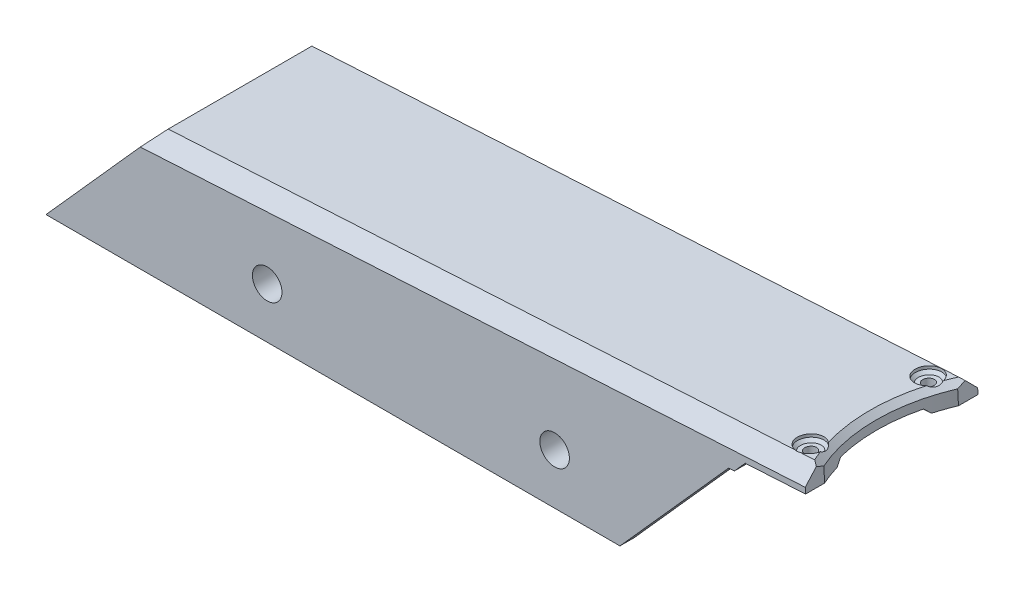
SolidWorks part; units mm, degrees
ref_plane "Plan de face" through (0, 0, 0) normal (0, 0, 1) x (1, 0, 0)
ref_plane "Plan de dessus" through (0, 0, 0) normal (0, 1, 0) x (1, 0, 0)
ref_plane "Plan de droite" through (0, 0, 0) normal (1, 0, 0) x (0, 0, -1)
sketch "Esquisse1" plane through (0, 0, 0) normal (0, 0, 1) x (1, 0, 0)
  line L0 (-49.925, 0) -> (49.925, 0)
  line L1 (-49.925, 0) -> (-36.817, 14.6872)
  line L2 (49.925, 0) -> (68.3667, 20.6636)
  line L3 (68.3667, 20.6636) -> (-36.817, 14.6872)
  point P4 (0, 0)
  dimension "D1" = 99.85
  dimension "D2" = 131.748
  dimension "D3" = 45
  dimension "D4" = 48.252
  dimension "D5" = 19.6859
extrude "Boss.-Extru.1" add sketch "Esquisse1" against normal blind 5
sketch "Esquisse2" plane through (0, 0, 0) normal (0, 0, 1) x (1, 0, 0)
  line L0 (-36.817, 14.6872) -> (68.3667, 20.6636)
  line L1 (68.3667, 20.6636) -> (-36.817, 14.6872) construction
  line L2 (68.3667, 20.6636) -> (74.0167, 26.9943)
  line L3 (74.0167, 26.9943) -> (-31.1671, 21.0179)
  line L4 (-31.1671, 21.0179) -> (-36.817, 14.6872)
  line L5 (-36.817, 14.6872) -> (-49.925, 0) construction
  line L6 (49.925, 0) -> (68.3667, 20.6636) construction
  line L11 (74.0167, 26.9943) -> (82.0167, 27.4488)
  line L12 (82.0167, 27.4488) -> (82.1585, 24.9528)
  line L13 (82.1585, 24.9528) -> (71.6625, 24.3565)
  line L22 (71.6625, 24.3565) -> (74.0167, 26.9943)
  dimension "D1" = 2.5
  dimension "D2" = 6
  dimension "D4" = 45
  dimension "D5" = 8
extrude "Boss.-Extru.2" add sketch "Esquisse2" against normal blind 5 contours L3 L4 L0 L2 | L13 L12 L11 L2 region at (18.5998, 20.8408, 0) region at (77.4387, 25.8804, 0)
sketch "Esquisse3" plane through (0, 0, -5) normal (0, 0, -1) x (-1, 0, 0)
  line L0 (-82.0167, 27.4488) -> (31.1671, 21.0179)
  line L1 (-82.0167, 27.4488) -> (31.1671, 21.0179) construction
  line L2 (-82.0167, 27.4488) -> (-82.1585, 24.9528)
  line L3 (-82.1585, 24.9528) -> (33.5212, 18.3801)
  line L4 (33.5212, 18.3801) -> (31.1671, 21.0179)
  line L5 (-82.0167, 27.4488) -> (-82.1585, 24.9528) construction
  line L9 (31.1671, 21.0179) -> (49.925, 0) construction
extrude "Boss.-Extru.3" add sketch "Esquisse3" along normal blind 25
sketch "Esquisse4" plane through (-1.1488, 20.2195, 0) normal (0.0567, -0.9984, 0) x (0.9984, 0.0567, 0)
  line L0 (83.4417, 0) -> (72.9288, 0)
  line L1 (72.9288, 0) -> (72.9288, -7.8)
  line L2 (72.9288, -7.8) -> (83.4417, -7.8)
  line L3 (83.4417, -7.8) -> (83.4417, 0)
  line L4 (83.4417, -30) -> (83.4417, 0) construction
  line L5 (83.4417, 0) -> (72.9288, 0) construction
  line L6 (72.9288, -5) -> (72.9288, 0) construction
  line L7 (72.9288, -22.2) -> (83.4417, -22.2)
  line L12 (100.4529, -15) -> (66.4305, -15) construction
  line L13 (72.9288, -30) -> (72.9288, -22.2)
  line L14 (83.4417, -30) -> (72.9288, -30)
  line L15 (83.4417, -22.2) -> (83.4417, -30)
  point P20 (83.4417, -15)
  dimension "D1" = 7.8
extrude "Boss.-Extru.4" add sketch "Esquisse4" along normal blind 1
sketch "Esquisse5" plane through (-1.1488, 20.2195, 0) normal (0.0567, -0.9984, 0) x (0.9984, 0.0567, 0)
  circle A0 centre (79.7412, -25.2117) radius 1
  circle A1 centre (79.7412, -4.7117) radius 1
  dimension "D1" = 2
extrude "Enlèv. mat.-Extru.1" cut sketch "Esquisse5" against normal through all both and the other way through all contours A1 | A0
sketch "Esquisse9" plane through (-1.2907, 22.7155, 0) normal (-0.0567, 0.9984, 0) x (0.9984, 0.0567, 0)
  circle A0 centre (79.7412, 25.2117) radius 2.25
  circle A1 centre (79.7412, 4.7117) radius 2.25
  dimension "D1" = 4.5
extrude "Enlèv. mat.-Extru.2" cut sketch "Esquisse9" against normal blind 1
sketch "Esquisse6" plane through (-1.1488, 20.2195, 0) normal (0.0567, -0.9984, 0) x (0.9984, 0.0567, 0)
  line L0 (83.4417, -3.3188) -> (83.4417, -26.6046)
  line L4 (83.4417, -30) -> (83.4417, 0) construction
  arc A0 (83.4417, -26.6046) -> (83.4417, -3.3188) centre (108.7412, -14.9617) cw
  point P11 (83.4417, -14.9617)
  dimension "D1" = 27.85
extrude "Enlèv. mat.-Extru.3" cut sketch "Esquisse6" against normal through all and the other way through all
sketch "Esquisse13" plane through (0, 0, 0) normal (0, 0, 1) x (1, 0, 0)
  circle A0 centre (38.5577, 8.8036) radius 2.575
  circle A1 centre (-11.4423, 8.8036) radius 2.575
  dimension "D1" = 5.15
extrude "Enlèv. mat.-Extru.4" cut sketch "Esquisse13" against normal through all both and the other way through all
sketch "Esquisse7" plane through (-1.1488, 20.2195, 0) normal (0.0567, -0.9984, 0) x (0.9984, 0.0567, 0)
  line L0 (72.9288, 0) -> (72.9288, -30)
  line L1 (72.9288, -30) -> (-32.4246, -30)
  line L2 (-32.4246, -30) -> (-32.4246, 0)
  line L3 (-32.4246, 0) -> (72.9288, 0)
  line L4 (-32.4246, -30) -> (72.9288, -30) construction
  line L6 (83.4417, 0) -> (-29.9246, 0) construction
  line L7 (-32.4246, -30) -> (-32.4246, -5) construction
  line L8 (72.9288, 0) -> (72.9288, -7.8) construction
extrude "Boss.-Extru.5" add sketch "Esquisse7" along normal blind 3
chamfer "Chanfrein1" distance 2.5 angle 45 1 edges at (-41.7231, 9.1901, -5)
chamfer "Chanfrein2" distance 2.5 angle 45 1 edges at (59.3813, 10.5956, -5)
chamfer "Chanfrein3" distance 2.7 angle 60 1 edges at (16.2457, 18.203, -5) first distance on face at (35.9827, 8.8036, -5)
chamfer "Chanfrein4" distance 2.5 angle 45 1 edges at (25.4248, 24.2334, 0)
chamfer "Chanfrein5" distance 2.5 angle 45 1 edges at (25.4248, 24.2334, -30)
chamfer "Chanfrein6" distance 0.5 angle 45 2 edges at (76.1325, 26.1129, -4.7117) (76.1325, 26.1129, -25.2117)
chamfer "Chanfrein7" distance 1 angle 45 1 edges at (79.4703, 27.3041, -14.9617)
chamfer "Chanfrein8" distance 2 angle 45 2 edges at (71.8327, 21.3613, -15) (19.2408, 18.3731, -30)
chamfer "Chanfrein9" distance 1 angle 45 1 edges at (76.1616, 23.6105, -7.8)
chamfer "Chanfrein10" distance 1 angle 45 1 edges at (76.1718, 23.6111, -22.2)
equation "\"3.50mm-\"=3.5"
